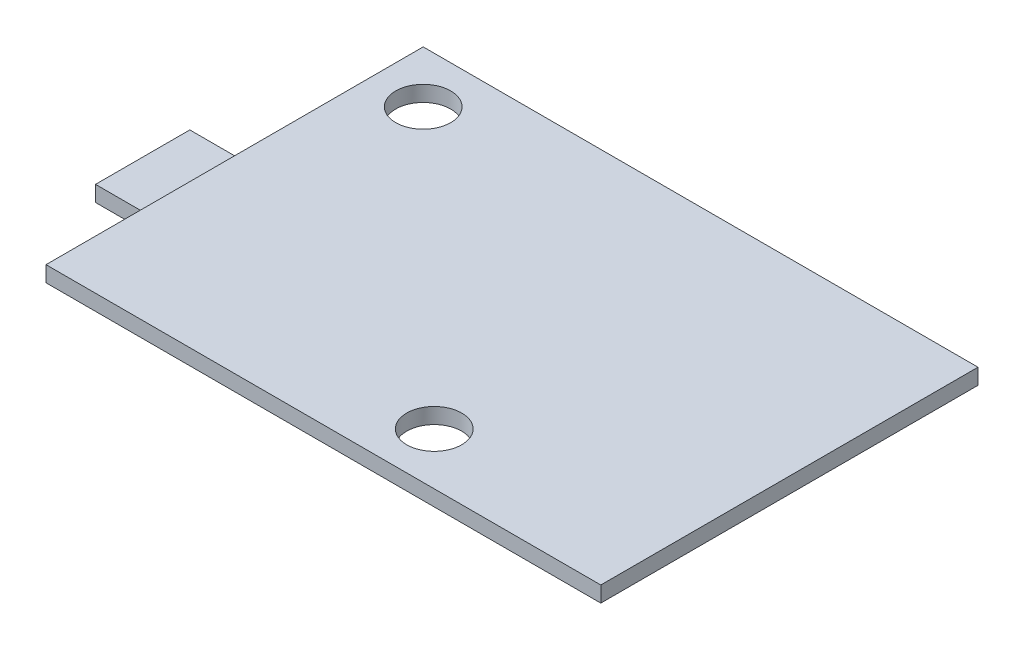
SolidWorks part; units mm, degrees
ref_plane "Спереди" through (0, 0, 0) normal (0, 0, 1) x (1, 0, 0)
ref_plane "Сверху" through (0, 0, 0) normal (0, 1, 0) x (1, 0, 0)
ref_plane "Справа" through (0, 0, 0) normal (1, 0, 0) x (0, 0, -1)
sketch "Sketch1" plane through (0, 0, 0) normal (0, 1, 0) x (1, 0, 0)
  line L1 (-17.65, -12) -> (17.65, -12)
  line L2 (-17.65, -12) -> (-17.65, 12)
  line L3 (-17.65, 12) -> (17.65, 12)
  line L4 (17.65, -12) -> (17.65, 12)
  line L5 (-17.65, -12) -> (17.65, 12) construction
  line L6 (-17.65, 12) -> (17.65, -12) construction
  point P0 (0, 0)
  dimension "D1" = 35.3
  dimension "D2" = 24
extrude "Boss-Extrude1" add sketch "Sketch1" along normal blind 1
hole_wizard "Ø3.5 (3.5) Diameter Hole1" positions "Sketch3" profile "Sketch4" hole size "Ø3.5" standard "ANSI Metric" end condition up to next
sketch "Sketch3" plane through (0, 1, 0) normal (0, 1, 0) x (1, 0, 0)
  line L0 (17.65, 12) -> (-17.65, 12) construction
  line L1 (-17.65, 12) -> (-17.65, -12) construction
  line L4 (-17.65, -12) -> (17.65, -12) construction
  point P0 (-14.35, 8.7)
  point P2 (3.75, -8.7)
  dimension "D1" = 3.3
  dimension "D2" = 3.3
  dimension "D3" = 21.4
  dimension "D4" = 3.3
sketch "Sketch4" plane through (-14.35, 1, -8.7) normal (1, 0, 0) x (0, 0, 1)
  line L0 (0, 0) -> (0, 1)
  line L1 (0, 1) -> (1.75, 1)
  line L2 (1.75, 1) -> (1.75, 0)
  line L5 (1.75, 0) -> (0, 0)
  line L11 (0, -6.35) -> (0, 107.95) construction
  dimension "Thru Hole Dia." = 3.5
  dimension "Thru Hole Depth" = 1
sketch "Sketch5" plane through (0, 0, 0) normal (0, -1, 0) x (1, 0, 0)
  line L9 (0, 0) -> (0, 1) construction
  line L10 (17.65, -12) -> (-17.65, -12) construction
  line L13 (-0.5, -2) -> (0.5, -2)
  line L14 (-0.5, -2) -> (-0.5, 4)
  line L15 (-0.5, 4) -> (0.5, 4)
  line L16 (0.5, -2) -> (0.5, 4)
  line L17 (-0.5, -2) -> (0.5, 4) construction
  line L18 (-0.5, 4) -> (0.5, -2) construction
  dimension "D1" = 10
  dimension "D2" = 6
  dimension "D3" = 1
extrude "Boss-Extrude2" add sketch "Sketch5" along normal blind 2
sketch "Sketch6" plane through (-0.5, 0, 0) normal (-1, 0, 0) x (0, 0, 1)
  line L0 (4, -2) -> (4, 0) construction
  line L1 (-2, -2) -> (4, -2)
  line L2 (-2, -2) -> (-2, -1)
  line L3 (-2, -1) -> (4, -1)
  line L4 (4, -2) -> (4, -1)
extrude "Boss-Extrude3" add sketch "Sketch6" along normal blind 22
fillet "Fillet1" radius 1 1 edges at (-0.5, -1, 1)
fillet "Fillet2" radius 2 1 edges at (0.5, -2, 1)
